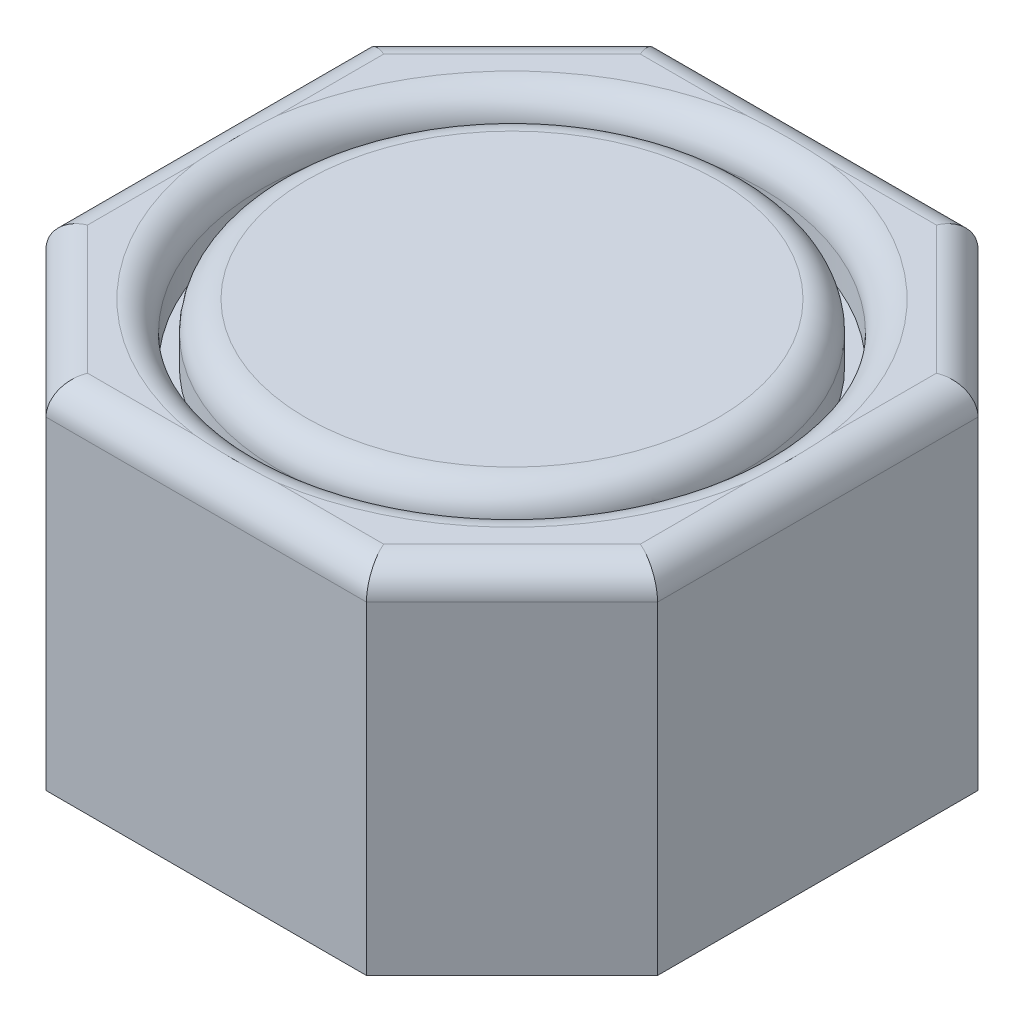
SolidWorks part; units mm, degrees
ref_plane "Front Plane" through (0, 0, 0) normal (0, 0, 1) x (1, 0, 0)
ref_plane "Top Plane" through (0, 0, 0) normal (0, 1, 0) x (1, 0, 0)
ref_plane "Right Plane" through (0, 0, 0) normal (1, 0, 0) x (0, 0, -1)
sketch "Sketch1" plane through (0, 0, 0) normal (0, 1, 0) x (1, 0, 0)
  line L0 (-2.6, 1.3626) -> (-1.3626, 2.6)
  line L1 (-1.3626, -2.6) -> (1.3626, -2.6)
  line L2 (-2.6, -1.3626) -> (-2.6, 1.3626)
  line L3 (-1.3626, 2.6) -> (1.3626, 2.6)
  line L4 (2.6, -1.3626) -> (2.6, 1.3626)
  line L5 (-1.9813, -1.9813) -> (1.9813, 1.9813) construction
  line L6 (-1.9813, 1.9813) -> (1.9813, -1.9813) construction
  line L7 (1.3626, 2.6) -> (2.6, 1.3626)
  line L8 (-2.6, -1.3626) -> (-1.3626, -2.6)
  line L9 (1.3626, -2.6) -> (2.6, -1.3626)
  point P0 (0, 0)
  dimension "D2" = 1.75
extrude "Boss-Extrude1" add sketch "Sketch1" along normal blind 3
sketch "Sketch2" plane through (0, 3, 0) normal (0, 1, 0) x (1, 0, 0)
  circle A0 centre (0, 0) radius 2
  circle A1 centre (0, 0) radius 2.1259
  dimension "D1" = 4
extrude "Cut-Extrude1" cut sketch "Sketch2" against normal blind 0.5 contours A1 A0 region at (-2.0658, 3, 0)
fillet "Fillet1" radius 0.25 10 edges at (-1.9813, 3, -1.9813) (0, 3, -2.6) (1.9813, 3, -1.9813) (2.6, 3, 0) (1.9813, 3, 1.9813) (0, 3, 2.6) (-1.9813, 3, 1.9813) (-2.6, 3, 0) (0, 3, 2.1259) (0, 3, 2)
